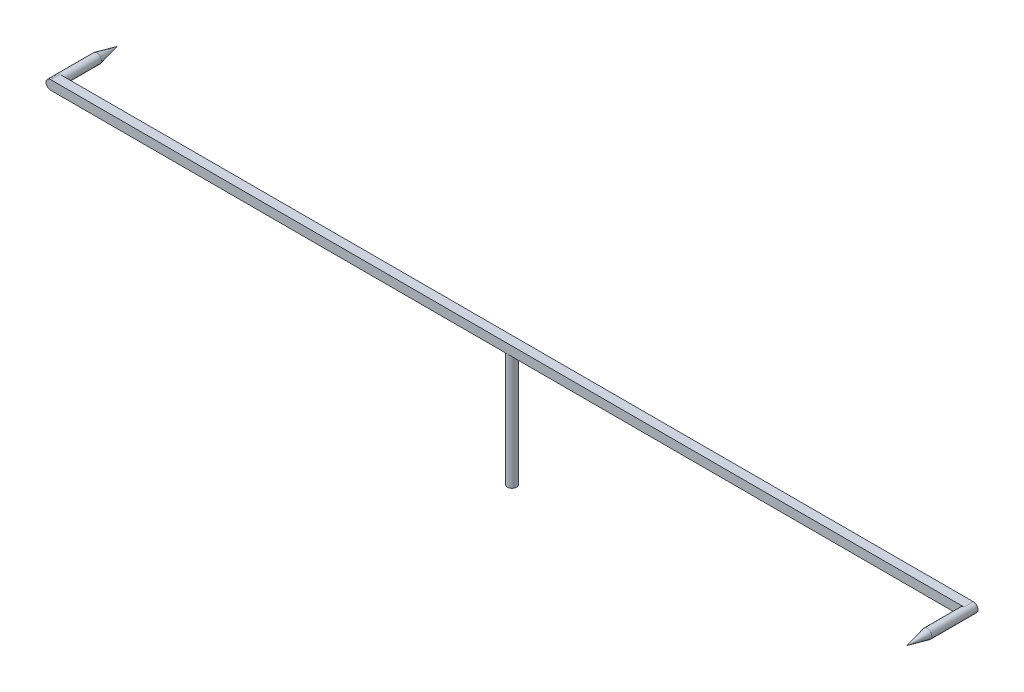
SolidWorks part; units mm, degrees
ref_plane "前视基准面" through (0, 0, 0) normal (0, 0, 1) x (1, 0, 0)
ref_plane "上视基准面" through (0, 0, 0) normal (0, 1, 0) x (1, 0, 0)
ref_plane "右视基准面" through (0, 0, 0) normal (1, 0, 0) x (0, 0, -1)
sketch "草图1" plane through (0, 0, 0) normal (0, 1, 0) x (1, 0, 0)
  circle A0 centre (0, 0) radius 0.4
  dimension "D1" = 0.8
extrude "凸台-拉伸1" add sketch "草图1" along normal blind 10
sketch "草图2" plane through (0, 10, 0) normal (0, 1, 0) x (1, 0, 0)
  line L1 (-40, 0.4) -> (40, 0.4)
  line L2 (-40, 0.4) -> (-40, -0.4)
  line L3 (-40, -0.4) -> (40, -0.4)
  line L4 (40, 0.4) -> (40, -0.4)
  circle A0 centre (0, 0) radius 0.4 construction
  dimension "D1" = 40
  dimension "D2" = 40
extrude "凸台-拉伸2" add sketch "草图2" along normal blind 0.8
fillet "圆角1" radius 0.4 4 edges at (40, 10, 0) (40, 10.8, 0) (-40, 10, 0) (-40, 10.8, 0)
sketch "草图3" plane through (0, 0, 0.4) normal (0, 0, 1) x (1, 0, 0)
  circle A0 centre (39.6, 10.4) radius 0.4
  dimension "D1" = 0.8
extrude "凸台-拉伸3" add sketch "草图3" along normal blind 3.2
sketch "草图4" plane through (0, 0, -0.4) normal (0, 0, -1) x (-1, 0, 0)
  circle A0 centre (39.6, 10.4) radius 0.4
  dimension "D1" = 0.8
extrude "凸台-拉伸4" add sketch "草图4" along normal blind 3.2
ref_plane "基准面1" through (0, 10.4, 0) normal (0, 1, 0) x (1, 0, 0)
sketch "草图5" plane through (0, 10.4, 0) normal (0, 1, 0) x (1, 0, 0)
  line L0 (39.6, -3.6) -> (39.6, -5.4)
  line L1 (39.2, -3.6) -> (40, -3.6) construction
  line L2 (40, -3.6) -> (39.6, -5.4)
  line L3 (39.6, -3.6) -> (40, -3.6)
  dimension "D1" = 1.8
revolve "旋转1" add sketch "草图5" angle 360 about L0
sketch "草图6" plane through (0, 10.4, 0) normal (0, 1, 0) x (1, 0, 0)
  line L0 (-39.6, 3.6) -> (-39.6, 5.4)
  line L1 (-39.2, 3.6) -> (-40, 3.6) construction
  line L2 (-39.6, 5.4) -> (-40, 3.6)
  line L3 (-40, 3.6) -> (-39.6, 3.6)
  dimension "D1" = 1.8
revolve "旋转2" add sketch "草图6" angle 360 about L0
